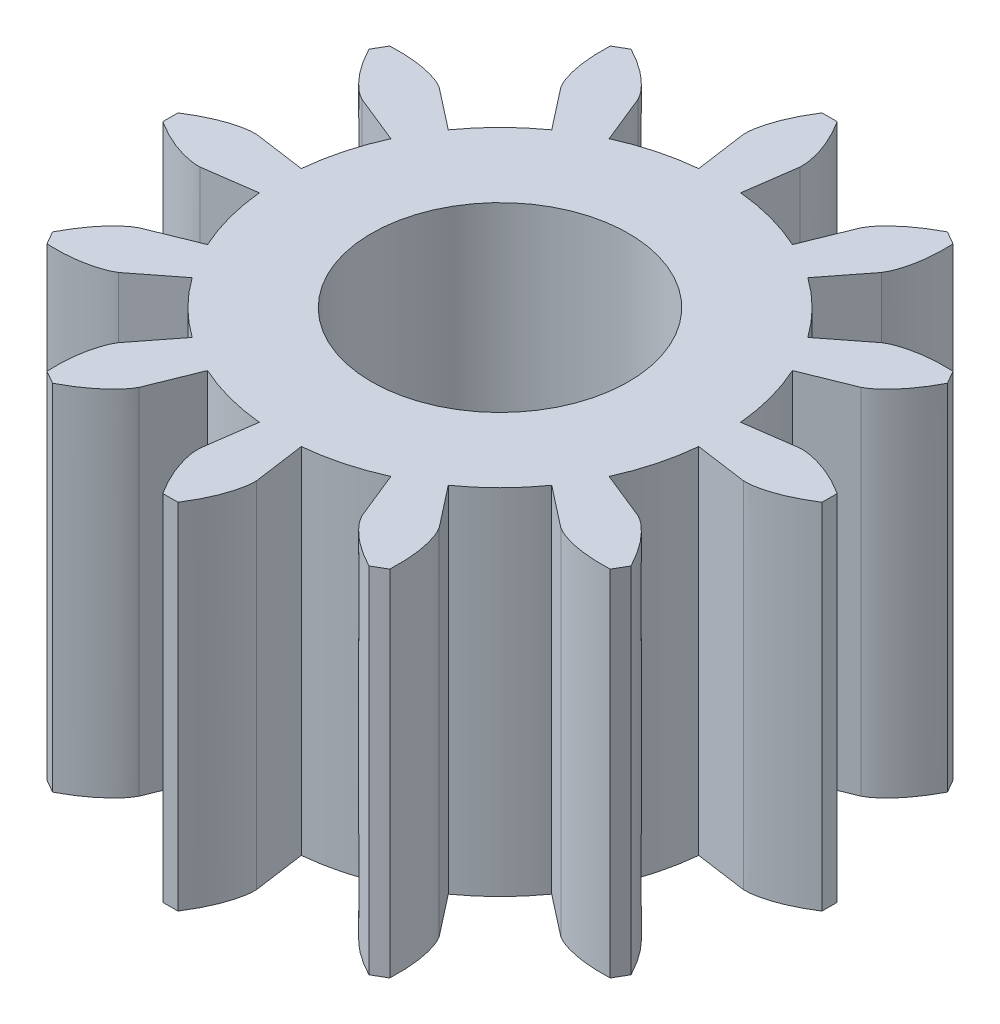
SolidWorks part; units mm, degrees
ref_plane "Front Plane" through (0, 0, 0) normal (0, 0, 1) x (1, 0, 0)
ref_plane "Top Plane" through (0, 0, 0) normal (0, 1, 0) x (1, 0, 0)
ref_plane "Right Plane" through (0, 0, 0) normal (1, 0, 0) x (0, 0, -1)
ref_plane "Plane1" through (0, -5, 0) normal (0, -1, 0) x (1, 0, 0)
sketch "Sketch1" plane through (0, -5, 0) normal (0, -1, 0) x (1, 0, 0)
  line L0 (3.7441, -2.923) -> (4.4442, -3.4696)
  line L1 (5.9256, -3.7266) -> (6.1901, -3.2684)
  line L2 (5.2268, -2.114) -> (4.4035, -1.781)
  line L3 (4.704, -0.6593) -> (5.5836, -0.7826)
  line L4 (6.995, -0.2646) -> (6.995, 0.2646)
  line L5 (5.5836, 0.7826) -> (4.704, 0.6593)
  line L6 (4.4035, 1.781) -> (5.2268, 2.114)
  line L7 (6.1901, 3.2684) -> (5.9256, 3.7266)
  line L8 (4.4442, 3.4696) -> (3.7441, 2.923)
  line L9 (2.923, 3.7441) -> (3.4696, 4.4442)
  line L10 (3.7266, 5.9256) -> (3.2684, 6.1901)
  line L11 (2.114, 5.2268) -> (1.781, 4.4035)
  line L12 (0.6593, 4.704) -> (0.7826, 5.5836)
  line L13 (0.2646, 6.995) -> (-0.2646, 6.995)
  line L14 (-0.7826, 5.5836) -> (-0.6593, 4.704)
  line L15 (-1.781, 4.4035) -> (-2.114, 5.2268)
  line L16 (-3.2684, 6.1901) -> (-3.7266, 5.9256)
  line L17 (-3.4696, 4.4442) -> (-2.923, 3.7441)
  line L18 (-3.7441, 2.923) -> (-4.4442, 3.4696)
  line L19 (-5.9256, 3.7266) -> (-6.1901, 3.2684)
  line L20 (-5.2268, 2.114) -> (-4.4035, 1.781)
  line L21 (-4.704, 0.6593) -> (-5.5836, 0.7826)
  line L22 (-6.995, 0.2646) -> (-6.995, -0.2646)
  line L23 (-5.5836, -0.7826) -> (-4.704, -0.6593)
  line L24 (-4.4035, -1.781) -> (-5.2268, -2.114)
  line L25 (-6.1901, -3.2684) -> (-5.9256, -3.7266)
  line L26 (-4.4442, -3.4696) -> (-3.7441, -2.923)
  line L27 (-2.923, -3.7441) -> (-3.4696, -4.4442)
  line L28 (-3.7266, -5.9256) -> (-3.2684, -6.1901)
  line L29 (-2.114, -5.2268) -> (-1.781, -4.4035)
  line L30 (-0.6593, -4.704) -> (-0.7826, -5.5836)
  line L31 (-0.2646, -6.995) -> (0.2646, -6.995)
  line L32 (0.7826, -5.5836) -> (0.6593, -4.704)
  line L33 (1.781, -4.4035) -> (2.114, -5.2268)
  line L34 (3.2684, -6.1901) -> (3.7266, -5.9256)
  line L35 (3.4696, -4.4442) -> (2.923, -3.7441)
  arc A0 (2.923, -3.7441) -> (3.7441, -2.923) centre (0, 0) ccw
  arc A1 (4.4035, -1.781) -> (4.704, -0.6593) centre (0, 0) ccw
  arc A2 (4.704, 0.6593) -> (4.4035, 1.781) centre (0, 0) ccw
  arc A3 (3.7441, 2.923) -> (2.923, 3.7441) centre (0, 0) ccw
  arc A4 (1.781, 4.4035) -> (0.6593, 4.704) centre (0, 0) ccw
  arc A5 (-0.6593, 4.704) -> (-1.781, 4.4035) centre (0, 0) ccw
  arc A6 (-2.923, 3.7441) -> (-3.7441, 2.923) centre (0, 0) ccw
  arc A7 (-4.4035, 1.781) -> (-4.704, 0.6593) centre (0, 0) ccw
  arc A8 (-4.704, -0.6593) -> (-4.4035, -1.781) centre (0, 0) ccw
  arc A9 (-3.7441, -2.923) -> (-2.923, -3.7441) centre (0, 0) ccw
  arc A10 (-1.781, -4.4035) -> (-0.6593, -4.704) centre (0, 0) ccw
  arc A11 (0.6593, -4.704) -> (1.781, -4.4035) centre (0, 0) ccw
  ellipse E0 centre (5.8654, -2.9875) end of major axis (7.546, -2.8631) minor radius 0.7415 (4.4442, -3.4696) -> (5.9256, -3.7266) ccw
  ellipse E1 centre (5.5279, -3.5513) end of major axis (6.2585, -5.0325) minor radius 0.7192 (6.1901, -3.2684) -> (5.2268, -2.114) ccw
  ellipse E2 centre (6.5733, 0.3454) end of major axis (7.9666, 1.2935) minor radius 0.7415 (5.5836, -0.7826) -> (6.995, -0.2646) ccw
  ellipse E3 centre (6.563, -0.3115) end of major axis (7.9362, -1.229) minor radius 0.7192 (6.995, 0.2646) -> (5.5836, 0.7826) ccw
  ellipse E4 centre (5.5199, 3.5858) end of major axis (4.7874, 2.068) minor radius 0.7415 (5.2268, 2.114) -> (6.1901, 3.2684) ccw
  ellipse E5 centre (5.8394, 3.0117) end of major axis (7.4875, 2.9038) minor radius 0.7192 (5.9256, 3.7266) -> (4.4442, 3.4696) ccw
  ellipse E6 centre (2.9875, 5.8654) end of major axis (3.112, 4.1847) minor radius 0.7415 (3.4696, 4.4442) -> (3.7266, 5.9256) ccw
  ellipse E7 centre (3.5513, 5.5279) end of major axis (5.0325, 6.2585) minor radius 0.7192 (3.2684, 6.1901) -> (2.114, 5.2268) ccw
  ellipse E8 centre (-0.3454, 6.5733) end of major axis (0.6027, 5.18) minor radius 0.7415 (0.7826, 5.5836) -> (0.2646, 6.995) ccw
  ellipse E9 centre (0.3115, 6.563) end of major axis (-0.606, 5.1897) minor radius 0.7192 (-0.2646, 6.995) -> (-0.7826, 5.5836) ccw
  ellipse E10 centre (-3.5858, 5.5199) end of major axis (-2.068, 4.7874) minor radius 0.7415 (-2.114, 5.2268) -> (-3.2684, 6.1901) ccw
  ellipse E11 centre (-3.0117, 5.8394) end of major axis (-3.1197, 4.1914) minor radius 0.7192 (-3.7266, 5.9256) -> (-3.4696, 4.4442) ccw
  ellipse E12 centre (-5.8654, 2.9875) end of major axis (-4.1847, 3.112) minor radius 0.7415 (-4.4442, 3.4696) -> (-5.9256, 3.7266) ccw
  ellipse E13 centre (-5.5279, 3.5513) end of major axis (-4.7974, 2.07) minor radius 0.7192 (-6.1901, 3.2684) -> (-5.2268, 2.114) ccw
  ellipse E14 centre (-6.5733, -0.3454) end of major axis (-5.18, 0.6027) minor radius 0.7415 (-5.5836, 0.7826) -> (-6.995, 0.2646) ccw
  ellipse E15 centre (-6.563, 0.3115) end of major axis (-5.1897, -0.606) minor radius 0.7192 (-6.995, -0.2646) -> (-5.5836, -0.7826) ccw
  ellipse E16 centre (-5.5199, -3.5858) end of major axis (-6.2525, -5.1035) minor radius 0.7415 (-5.2268, -2.114) -> (-6.1901, -3.2684) ccw
  ellipse E17 centre (-5.8394, -3.0117) end of major axis (-4.1914, -3.1197) minor radius 0.7192 (-5.9256, -3.7266) -> (-4.4442, -3.4696) ccw
  ellipse E18 centre (-2.9875, -5.8654) end of major axis (-2.8631, -7.546) minor radius 0.7415 (-3.4696, -4.4442) -> (-3.7266, -5.9256) ccw
  ellipse E19 centre (-3.5513, -5.5279) end of major axis (-5.0325, -6.2585) minor radius 0.7192 (-3.2684, -6.1901) -> (-2.114, -5.2268) ccw
  ellipse E20 centre (0.3454, -6.5733) end of major axis (1.2935, -7.9666) minor radius 0.7415 (-0.7826, -5.5836) -> (-0.2646, -6.995) ccw
  ellipse E21 centre (-0.3115, -6.563) end of major axis (-1.229, -7.9362) minor radius 0.7192 (0.2646, -6.995) -> (0.7826, -5.5836) ccw
  ellipse E22 centre (3.5858, -5.5199) end of major axis (5.1035, -6.2525) minor radius 0.7415 (2.114, -5.2268) -> (3.2684, -6.1901) ccw
  ellipse E23 centre (3.0117, -5.8394) end of major axis (2.9038, -7.4875) minor radius 0.7192 (3.7266, -5.9256) -> (3.4696, -4.4442) ccw
  point P4 (5.8654, -2.9875)
  point P5 (7.546, -2.8631)
  point P6 (5.9201, -3.727)
  point P7 (4.4442, -3.4696)
  point P8 (5.9256, -3.7266)
  point P9 (5.1439, -3.7018)
  point P10 (6.5868, -2.2732)
  point P18 (5.5279, -3.5513)
  point P19 (6.173, -3.2331)
  point P20 (6.2585, -5.0325)
  point P21 (6.1901, -3.2684)
  point P22 (5.2268, -2.114)
  point P23 (5.7778, -2.6038)
  point P24 (5.2781, -4.4987)
  point P34 (6.5733, 0.3454)
  point P35 (7.9666, 1.2935)
  point P36 (6.9905, -0.2677)
  point P37 (5.5836, -0.7826)
  point P38 (6.995, -0.2646)
  point P39 (6.3057, -0.6339)
  point P40 (6.8409, 1.3247)
  point P48 (6.563, -0.3115)
  point P49 (7.9362, -1.229)
  point P50 (6.1634, -0.9095)
  point P51 (6.995, 0.2646)
  point P52 (5.5836, 0.7826)
  point P53 (6.3057, 0.6339)
  point P54 (6.8203, -1.2569)
  point P64 (5.5199, 3.5858)
  point P65 (6.1878, 3.2634)
  point P66 (4.7874, 2.068)
  point P67 (5.2268, 2.114)
  point P68 (6.1901, 3.2684)
  point P69 (5.7778, 2.6038)
  point P70 (5.2621, 4.5677)
  point P78 (5.8394, 3.0117)
  point P79 (7.4875, 2.9038)
  point P80 (5.7924, 2.294)
  point P81 (5.9256, 3.7266)
  point P82 (4.4442, 3.4696)
  point P83 (5.1439, 3.7018)
  point P84 (6.535, 2.3216)
  point P94 (2.9875, 5.8654)
  point P95 (3.727, 5.9201)
  point P96 (3.112, 4.1847)
  point P97 (3.4696, 4.4442)
  point P98 (3.7266, 5.9256)
  point P99 (3.7018, 5.1439)
  point P100 (2.2732, 6.5868)
  point P108 (3.5513, 5.5279)
  point P109 (5.0325, 6.2585)
  point P110 (3.8694, 4.8829)
  point P111 (3.2684, 6.1901)
  point P112 (2.114, 5.2268)
  point P113 (2.6038, 5.7778)
  point P114 (4.4987, 5.2781)
  point P124 (-0.3454, 6.5733)
  point P125 (0.2677, 6.9905)
  point P126 (0.6027, 5.18)
  point P127 (0.7826, 5.5836)
  point P128 (0.2646, 6.995)
  point P129 (0.6339, 6.3057)
  point P130 (-1.3247, 6.8409)
  point P138 (0.3115, 6.563)
  point P139 (0.9095, 6.1634)
  point P140 (-0.606, 5.1897)
  point P141 (-0.2646, 6.995)
  point P142 (-0.7826, 5.5836)
  point P143 (-0.6339, 6.3057)
  point P144 (1.2569, 6.8203)
  point P154 (-3.5858, 5.5199)
  point P155 (-2.068, 4.7874)
  point P156 (-3.9081, 4.8521)
  point P157 (-2.114, 5.2268)
  point P158 (-3.2684, 6.1901)
  point P159 (-2.6038, 5.7778)
  point P160 (-4.5677, 5.2621)
  point P168 (-3.0117, 5.8394)
  point P169 (-2.294, 5.7924)
  point P170 (-3.1197, 4.1914)
  point P171 (-3.7266, 5.9256)
  point P172 (-3.4696, 4.4442)
  point P173 (-3.7018, 5.1439)
  point P174 (-2.3216, 6.535)
  point P184 (-5.8654, 2.9875)
  point P185 (-4.1847, 3.112)
  point P186 (-5.8106, 2.248)
  point P187 (-4.4442, 3.4696)
  point P188 (-5.9256, 3.7266)
  point P189 (-5.1439, 3.7018)
  point P190 (-6.5868, 2.2732)
  point P198 (-5.5279, 3.5513)
  point P199 (-4.8829, 3.8694)
  point P200 (-4.7974, 2.07)
  point P201 (-6.1901, 3.2684)
  point P202 (-5.2268, 2.114)
  point P203 (-5.7778, 2.6038)
  point P204 (-5.2781, 4.4987)
  point P214 (-6.5733, -0.3454)
  point P215 (-5.18, 0.6027)
  point P216 (-6.1561, -0.9585)
  point P217 (-5.5836, 0.7826)
  point P218 (-6.995, 0.2646)
  point P219 (-6.3057, 0.6339)
  point P220 (-6.8409, -1.3247)
  point P228 (-6.563, 0.3115)
  point P229 (-5.1897, -0.606)
  point P230 (-6.9625, -0.2865)
  point P231 (-6.995, -0.2646)
  point P232 (-5.5836, -0.7826)
  point P233 (-6.3057, -0.6339)
  point P234 (-6.8203, 1.2569)
  point P244 (-5.5199, -3.5858)
  point P245 (-4.8521, -3.9081)
  point P246 (-6.2525, -5.1035)
  point P247 (-5.2268, -2.114)
  point P248 (-6.1901, -3.2684)
  point P249 (-5.7778, -2.6038)
  point P250 (-5.2621, -4.5677)
  point P258 (-5.8394, -3.0117)
  point P259 (-4.1914, -3.1197)
  point P260 (-5.8865, -3.7294)
  point P261 (-5.9256, -3.7266)
  point P262 (-4.4442, -3.4696)
  point P263 (-5.1439, -3.7018)
  point P264 (-6.535, -2.3216)
  point P274 (-2.9875, -5.8654)
  point P275 (-2.248, -5.8106)
  point P276 (-2.8631, -7.546)
  point P277 (-3.4696, -4.4442)
  point P278 (-3.7266, -5.9256)
  point P279 (-3.7018, -5.1439)
  point P280 (-2.2732, -6.5868)
  point P288 (-3.5513, -5.5279)
  point P289 (-2.07, -4.7974)
  point P290 (-3.2331, -6.173)
  point P291 (-3.2684, -6.1901)
  point P292 (-2.114, -5.2268)
  point P293 (-2.6038, -5.7778)
  point P294 (-4.4987, -5.2781)
  point P304 (0.3454, -6.5733)
  point P305 (0.9585, -6.1561)
  point P306 (1.2935, -7.9666)
  point P307 (-0.7826, -5.5836)
  point P308 (-0.2646, -6.995)
  point P309 (-0.6339, -6.3057)
  point P310 (1.3247, -6.8409)
  point P318 (-0.3115, -6.563)
  point P319 (0.2865, -6.9625)
  point P320 (-1.229, -7.9362)
  point P321 (0.2646, -6.995)
  point P322 (0.7826, -5.5836)
  point P323 (0.6339, -6.3057)
  point P324 (-1.2569, -6.8203)
  point P334 (3.5858, -5.5199)
  point P335 (5.1035, -6.2525)
  point P336 (3.2634, -6.1878)
  point P337 (2.114, -5.2268)
  point P338 (3.2684, -6.1901)
  point P339 (2.6038, -5.7778)
  point P340 (4.5677, -5.2621)
  point P348 (3.0117, -5.8394)
  point P349 (3.7294, -5.8865)
  point P350 (2.9038, -7.4875)
  point P351 (3.7266, -5.9256)
  point P352 (3.4696, -4.4442)
  point P353 (3.7018, -5.1439)
  point P354 (2.3216, -6.535)
extrude "Boss-Extrude1" add sketch "Sketch1" against normal blind 5
sketch "Sketch3" plane through (0, 0, 0) normal (0, 1, 0) x (1, 0, 0)
  line L36 (2.923, 3.7441) -> (3.4696, 4.4442)
  line L37 (3.7266, 5.9256) -> (3.2684, 6.1901)
  line L38 (2.114, 5.2268) -> (1.781, 4.4035)
  line L39 (0.6593, 4.704) -> (0.7826, 5.5836)
  line L40 (0.2646, 6.995) -> (-0.2646, 6.995)
  line L41 (-0.7826, 5.5836) -> (-0.6593, 4.704)
  line L42 (-1.781, 4.4035) -> (-2.114, 5.2268)
  line L43 (-3.2684, 6.1901) -> (-3.7266, 5.9256)
  line L44 (-3.4696, 4.4442) -> (-2.923, 3.7441)
  line L45 (-3.7441, 2.923) -> (-4.4442, 3.4696)
  line L46 (-5.9256, 3.7266) -> (-6.1901, 3.2684)
  line L47 (-5.2268, 2.114) -> (-4.4035, 1.781)
  line L48 (-4.704, 0.6593) -> (-5.5836, 0.7826)
  line L49 (-6.995, 0.2646) -> (-6.995, -0.2646)
  line L50 (-5.5836, -0.7826) -> (-4.704, -0.6593)
  line L51 (-4.4035, -1.781) -> (-5.2268, -2.114)
  line L52 (-6.1901, -3.2684) -> (-5.9256, -3.7266)
  line L53 (-4.4442, -3.4696) -> (-3.7441, -2.923)
  line L54 (-2.923, -3.7441) -> (-3.4696, -4.4442)
  line L55 (-3.7266, -5.9256) -> (-3.2684, -6.1901)
  line L56 (-2.114, -5.2268) -> (-1.781, -4.4035)
  line L57 (-0.6593, -4.704) -> (-0.7826, -5.5836)
  line L58 (-0.2646, -6.995) -> (0.2646, -6.995)
  line L59 (0.7826, -5.5836) -> (0.6593, -4.704)
  line L60 (1.781, -4.4035) -> (2.114, -5.2268)
  line L61 (3.2684, -6.1901) -> (3.7266, -5.9256)
  line L62 (3.4696, -4.4442) -> (2.923, -3.7441)
  line L63 (3.7441, -2.923) -> (4.4442, -3.4696)
  line L64 (5.9256, -3.7266) -> (6.1901, -3.2684)
  line L65 (5.2268, -2.114) -> (4.4035, -1.781)
  line L66 (4.704, -0.6593) -> (5.5836, -0.7826)
  line L67 (6.995, -0.2646) -> (6.995, 0.2646)
  line L68 (5.5836, 0.7826) -> (4.704, 0.6593)
  line L69 (4.4035, 1.781) -> (5.2268, 2.114)
  line L70 (6.1901, 3.2684) -> (5.9256, 3.7266)
  line L71 (4.4442, 3.4696) -> (3.7441, 2.923)
  line L72 (2.923, 3.7441) -> (3.4696, 4.4442)
  line L73 (3.7266, 5.9256) -> (3.2684, 6.1901)
  line L74 (2.114, 5.2268) -> (1.781, 4.4035)
  line L75 (0.6593, 4.704) -> (0.7826, 5.5836)
  line L76 (0.2646, 6.995) -> (-0.2646, 6.995)
  line L77 (-0.7826, 5.5836) -> (-0.6593, 4.704)
  line L78 (-1.781, 4.4035) -> (-2.114, 5.2268)
  line L79 (-3.2684, 6.1901) -> (-3.7266, 5.9256)
  line L80 (-3.4696, 4.4442) -> (-2.923, 3.7441)
  line L81 (-3.7441, 2.923) -> (-4.4442, 3.4696)
  line L82 (-5.9256, 3.7266) -> (-6.1901, 3.2684)
  line L83 (-5.2268, 2.114) -> (-4.4035, 1.781)
  line L84 (-4.704, 0.6593) -> (-5.5836, 0.7826)
  line L85 (-6.995, 0.2646) -> (-6.995, -0.2646)
  line L86 (-5.5836, -0.7826) -> (-4.704, -0.6593)
  line L87 (-4.4035, -1.781) -> (-5.2268, -2.114)
  line L88 (-6.1901, -3.2684) -> (-5.9256, -3.7266)
  line L89 (-4.4442, -3.4696) -> (-3.7441, -2.923)
  line L90 (-2.923, -3.7441) -> (-3.4696, -4.4442)
  line L91 (-3.7266, -5.9256) -> (-3.2684, -6.1901)
  line L92 (-2.114, -5.2268) -> (-1.781, -4.4035)
  line L93 (-0.6593, -4.704) -> (-0.7826, -5.5836)
  line L94 (-0.2646, -6.995) -> (0.2646, -6.995)
  line L95 (0.7826, -5.5836) -> (0.6593, -4.704)
  line L96 (1.781, -4.4035) -> (2.114, -5.2268)
  line L97 (3.2684, -6.1901) -> (3.7266, -5.9256)
  line L98 (3.4696, -4.4442) -> (2.923, -3.7441)
  line L99 (3.7441, -2.923) -> (4.4442, -3.4696)
  line L100 (5.9256, -3.7266) -> (6.1901, -3.2684)
  line L101 (5.2268, -2.114) -> (4.4035, -1.781)
  line L102 (4.704, -0.6593) -> (5.5836, -0.7826)
  line L103 (6.995, -0.2646) -> (6.995, 0.2646)
  line L104 (5.5836, 0.7826) -> (4.704, 0.6593)
  line L105 (4.4035, 1.781) -> (5.2268, 2.114)
  line L106 (6.1901, 3.2684) -> (5.9256, 3.7266)
  line L107 (4.4442, 3.4696) -> (3.7441, 2.923)
  arc A12 (3.7441, 2.923) -> (2.923, 3.7441) centre (0, 0) ccw
  arc A13 (1.781, 4.4035) -> (0.6593, 4.704) centre (0, 0) ccw
  arc A14 (-0.6593, 4.704) -> (-1.781, 4.4035) centre (0, 0) ccw
  arc A15 (-2.923, 3.7441) -> (-3.7441, 2.923) centre (0, 0) ccw
  arc A16 (-4.4035, 1.781) -> (-4.704, 0.6593) centre (0, 0) ccw
  arc A17 (-4.704, -0.6593) -> (-4.4035, -1.781) centre (0, 0) ccw
  arc A18 (-3.7441, -2.923) -> (-2.923, -3.7441) centre (0, 0) ccw
  arc A19 (-1.781, -4.4035) -> (-0.6593, -4.704) centre (0, 0) ccw
  arc A20 (0.6593, -4.704) -> (1.781, -4.4035) centre (0, 0) ccw
  arc A21 (2.923, -3.7441) -> (3.7441, -2.923) centre (0, 0) ccw
  arc A22 (4.4035, -1.781) -> (4.704, -0.6593) centre (0, 0) ccw
  arc A23 (4.704, 0.6593) -> (4.4035, 1.781) centre (0, 0) ccw
  arc A24 (3.7441, 2.923) -> (2.923, 3.7441) centre (0, 0) ccw
  arc A25 (1.781, 4.4035) -> (0.6593, 4.704) centre (0, 0) ccw
  arc A26 (-0.6593, 4.704) -> (-1.781, 4.4035) centre (0, 0) ccw
  arc A27 (-2.923, 3.7441) -> (-3.7441, 2.923) centre (0, 0) ccw
  arc A28 (-4.4035, 1.781) -> (-4.704, 0.6593) centre (0, 0) ccw
  arc A29 (-4.704, -0.6593) -> (-4.4035, -1.781) centre (0, 0) ccw
  arc A30 (-3.7441, -2.923) -> (-2.923, -3.7441) centre (0, 0) ccw
  arc A31 (-1.781, -4.4035) -> (-0.6593, -4.704) centre (0, 0) ccw
  arc A32 (0.6593, -4.704) -> (1.781, -4.4035) centre (0, 0) ccw
  arc A33 (2.923, -3.7441) -> (3.7441, -2.923) centre (0, 0) ccw
  arc A34 (4.4035, -1.781) -> (4.704, -0.6593) centre (0, 0) ccw
  arc A35 (4.704, 0.6593) -> (4.4035, 1.781) centre (0, 0) ccw
  ellipse E24 centre (3.0117, 5.8394) end of major axis (2.9038, 7.4875) minor radius 0.7192 (3.4696, 4.4442) -> (3.7266, 5.9256) ccw
  ellipse E25 centre (3.5858, 5.5199) end of major axis (2.068, 4.7874) minor radius 0.7415 (3.2684, 6.1901) -> (2.114, 5.2268) ccw
  ellipse E26 centre (-0.3115, 6.563) end of major axis (-1.229, 7.9362) minor radius 0.7192 (0.7826, 5.5836) -> (0.2646, 6.995) ccw
  ellipse E27 centre (0.3454, 6.5733) end of major axis (1.2935, 7.9666) minor radius 0.7415 (-0.2646, 6.995) -> (-0.7826, 5.5836) ccw
  ellipse E28 centre (-3.5513, 5.5279) end of major axis (-2.07, 4.7974) minor radius 0.7192 (-2.114, 5.2268) -> (-3.2684, 6.1901) ccw
  ellipse E29 centre (-2.9875, 5.8654) end of major axis (-2.8631, 7.546) minor radius 0.7415 (-3.7266, 5.9256) -> (-3.4696, 4.4442) ccw
  ellipse E30 centre (-5.8394, 3.0117) end of major axis (-4.1914, 3.1197) minor radius 0.7192 (-4.4442, 3.4696) -> (-5.9256, 3.7266) ccw
  ellipse E31 centre (-5.5199, 3.5858) end of major axis (-6.2525, 5.1035) minor radius 0.7415 (-6.1901, 3.2684) -> (-5.2268, 2.114) ccw
  ellipse E32 centre (-6.563, -0.3115) end of major axis (-5.1897, 0.606) minor radius 0.7192 (-5.5836, 0.7826) -> (-6.995, 0.2646) ccw
  ellipse E33 centre (-6.5733, 0.3454) end of major axis (-7.9666, 1.2935) minor radius 0.7415 (-6.995, -0.2646) -> (-5.5836, -0.7826) ccw
  ellipse E34 centre (-5.5279, -3.5513) end of major axis (-6.2585, -5.0325) minor radius 0.7192 (-5.2268, -2.114) -> (-6.1901, -3.2684) ccw
  ellipse E35 centre (-5.8654, -2.9875) end of major axis (-4.1847, -3.112) minor radius 0.7415 (-5.9256, -3.7266) -> (-4.4442, -3.4696) ccw
  ellipse E36 centre (-3.0117, -5.8394) end of major axis (-3.1197, -4.1914) minor radius 0.7192 (-3.4696, -4.4442) -> (-3.7266, -5.9256) ccw
  ellipse E37 centre (-3.5858, -5.5199) end of major axis (-5.1035, -6.2525) minor radius 0.7415 (-3.2684, -6.1901) -> (-2.114, -5.2268) ccw
  ellipse E38 centre (0.3115, -6.563) end of major axis (-0.606, -5.1897) minor radius 0.7192 (-0.7826, -5.5836) -> (-0.2646, -6.995) ccw
  ellipse E39 centre (-0.3454, -6.5733) end of major axis (0.6027, -5.18) minor radius 0.7415 (0.2646, -6.995) -> (0.7826, -5.5836) ccw
  ellipse E40 centre (3.5513, -5.5279) end of major axis (5.0325, -6.2585) minor radius 0.7192 (2.114, -5.2268) -> (3.2684, -6.1901) ccw
  ellipse E41 centre (2.9875, -5.8654) end of major axis (3.112, -4.1847) minor radius 0.7415 (3.7266, -5.9256) -> (3.4696, -4.4442) ccw
  ellipse E42 centre (5.8394, -3.0117) end of major axis (7.4875, -2.9038) minor radius 0.7192 (4.4442, -3.4696) -> (5.9256, -3.7266) ccw
  ellipse E43 centre (5.5199, -3.5858) end of major axis (4.7874, -2.068) minor radius 0.7415 (6.1901, -3.2684) -> (5.2268, -2.114) ccw
  ellipse E44 centre (6.563, 0.3115) end of major axis (7.9362, 1.229) minor radius 0.7192 (5.5836, -0.7826) -> (6.995, -0.2646) ccw
  ellipse E45 centre (6.5733, -0.3454) end of major axis (7.9666, -1.2935) minor radius 0.7415 (6.995, 0.2646) -> (5.5836, 0.7826) ccw
  ellipse E46 centre (5.5279, 3.5513) end of major axis (6.2585, 5.0325) minor radius 0.7192 (5.2268, 2.114) -> (6.1901, 3.2684) ccw
  ellipse E47 centre (5.8654, 2.9875) end of major axis (7.546, 2.8631) minor radius 0.7415 (5.9256, 3.7266) -> (4.4442, 3.4696) ccw
  ellipse E48 centre (3.0117, 5.8394) end of major axis (2.9038, 7.4875) minor radius 0.7192 (3.4696, 4.4442) -> (3.7266, 5.9256) ccw
  ellipse E49 centre (3.5858, 5.5199) end of major axis (5.1035, 6.2525) minor radius 0.7415 (3.2684, 6.1901) -> (2.114, 5.2268) ccw
  ellipse E50 centre (-0.3115, 6.563) end of major axis (-1.229, 7.9362) minor radius 0.7192 (0.7826, 5.5836) -> (0.2646, 6.995) ccw
  ellipse E51 centre (0.3454, 6.5733) end of major axis (1.2935, 7.9666) minor radius 0.7415 (-0.2646, 6.995) -> (-0.7826, 5.5836) ccw
  ellipse E52 centre (-3.5513, 5.5279) end of major axis (-2.07, 4.7974) minor radius 0.7192 (-2.114, 5.2268) -> (-3.2684, 6.1901) ccw
  ellipse E53 centre (-2.9875, 5.8654) end of major axis (-2.8631, 7.546) minor radius 0.7415 (-3.7266, 5.9256) -> (-3.4696, 4.4442) ccw
  ellipse E54 centre (-5.8394, 3.0117) end of major axis (-4.1914, 3.1197) minor radius 0.7192 (-4.4442, 3.4696) -> (-5.9256, 3.7266) ccw
  ellipse E55 centre (-5.5199, 3.5858) end of major axis (-6.2525, 5.1035) minor radius 0.7415 (-6.1901, 3.2684) -> (-5.2268, 2.114) ccw
  ellipse E56 centre (-6.563, -0.3115) end of major axis (-5.1897, 0.606) minor radius 0.7192 (-5.5836, 0.7826) -> (-6.995, 0.2646) ccw
  ellipse E57 centre (-6.5733, 0.3454) end of major axis (-7.9666, 1.2935) minor radius 0.7415 (-6.995, -0.2646) -> (-5.5836, -0.7826) ccw
  ellipse E58 centre (-5.5279, -3.5513) end of major axis (-6.2585, -5.0325) minor radius 0.7192 (-5.2268, -2.114) -> (-6.1901, -3.2684) ccw
  ellipse E59 centre (-5.8654, -2.9875) end of major axis (-4.1847, -3.112) minor radius 0.7415 (-5.9256, -3.7266) -> (-4.4442, -3.4696) ccw
  ellipse E60 centre (-3.0117, -5.8394) end of major axis (-3.1197, -4.1914) minor radius 0.7192 (-3.4696, -4.4442) -> (-3.7266, -5.9256) ccw
  ellipse E61 centre (-3.5858, -5.5199) end of major axis (-5.1035, -6.2525) minor radius 0.7415 (-3.2684, -6.1901) -> (-2.114, -5.2268) ccw
  ellipse E62 centre (0.3115, -6.563) end of major axis (-0.606, -5.1897) minor radius 0.7192 (-0.7826, -5.5836) -> (-0.2646, -6.995) ccw
  ellipse E63 centre (-0.3454, -6.5733) end of major axis (0.6027, -5.18) minor radius 0.7415 (0.2646, -6.995) -> (0.7826, -5.5836) ccw
  ellipse E64 centre (3.5513, -5.5279) end of major axis (5.0325, -6.2585) minor radius 0.7192 (2.114, -5.2268) -> (3.2684, -6.1901) ccw
  ellipse E65 centre (2.9875, -5.8654) end of major axis (3.112, -4.1847) minor radius 0.7415 (3.7266, -5.9256) -> (3.4696, -4.4442) ccw
  ellipse E66 centre (5.8394, -3.0117) end of major axis (7.4875, -2.9038) minor radius 0.7192 (4.4442, -3.4696) -> (5.9256, -3.7266) ccw
  ellipse E67 centre (5.5199, -3.5858) end of major axis (4.7874, -2.068) minor radius 0.7415 (6.1901, -3.2684) -> (5.2268, -2.114) ccw
  ellipse E68 centre (6.563, 0.3115) end of major axis (7.9362, 1.229) minor radius 0.7192 (5.5836, -0.7826) -> (6.995, -0.2646) ccw
  ellipse E69 centre (6.5733, -0.3454) end of major axis (7.9666, -1.2935) minor radius 0.7415 (6.995, 0.2646) -> (5.5836, 0.7826) ccw
  ellipse E70 centre (5.5279, 3.5513) end of major axis (6.2585, 5.0325) minor radius 0.7192 (5.2268, 2.114) -> (6.1901, 3.2684) ccw
  ellipse E71 centre (5.8654, 2.9875) end of major axis (7.546, 2.8631) minor radius 0.7415 (5.9256, 3.7266) -> (4.4442, 3.4696) ccw
  dimension "D1" = 0
extrude "Boss-Extrude2" add sketch "Sketch3" along normal blind 2.3
sketch "Sketch2" plane through (0, -5, 0) normal (0, 1, 0) x (1, 0, 0)
  line L0 (0.4329, 4.5294) -> (0.5832, 5.6016)
  line L1 (0.1571, 6.795) -> (-0.1571, 6.795)
  line L2 (-0.5832, 5.6015) -> (-0.4329, 4.5294)
  line L3 (-1.8898, 4.139) -> (-2.2957, 5.1427)
  line L4 (-3.2614, 5.9632) -> (-3.5336, 5.8061)
  line L5 (-3.3058, 4.5594) -> (-2.6396, 3.7061)
  line L6 (-3.7061, 2.6396) -> (-4.5595, 3.3059)
  line L7 (-5.8061, 3.5336) -> (-5.9632, 3.2614)
  line L8 (-5.1426, 2.2957) -> (-4.139, 1.8898)
  line L9 (-4.5294, 0.4329) -> (-5.6016, 0.5832)
  line L10 (-6.795, 0.1571) -> (-6.795, -0.1571)
  line L11 (-5.6015, -0.5832) -> (-4.5294, -0.4329)
  line L12 (-4.139, -1.8898) -> (-5.1427, -2.2957)
  line L13 (-5.9632, -3.2614) -> (-5.8061, -3.5336)
  line L14 (-4.5594, -3.3058) -> (-3.7061, -2.6396)
  line L15 (-2.6396, -3.7061) -> (-3.3059, -4.5595)
  line L16 (-3.5336, -5.8061) -> (-3.2614, -5.9632)
  line L17 (-2.2957, -5.1426) -> (-1.8898, -4.139)
  line L18 (-0.4329, -4.5294) -> (-0.5832, -5.6016)
  line L19 (-0.1571, -6.795) -> (0.1571, -6.795)
  line L20 (0.5832, -5.6015) -> (0.4329, -4.5294)
  line L21 (1.8898, -4.139) -> (2.2957, -5.1427)
  line L22 (3.2614, -5.9632) -> (3.5336, -5.8061)
  line L23 (3.3058, -4.5594) -> (2.6396, -3.7061)
  line L24 (3.7061, -2.6396) -> (4.5595, -3.3059)
  line L25 (5.8061, -3.5336) -> (5.9632, -3.2614)
  line L26 (5.1426, -2.2957) -> (4.139, -1.8898)
  line L27 (4.5294, -0.4329) -> (5.6016, -0.5832)
  line L28 (6.795, -0.1571) -> (6.795, 0.1571)
  line L29 (5.6015, 0.5832) -> (4.5294, 0.4329)
  line L30 (4.139, 1.8898) -> (5.1427, 2.2957)
  line L31 (5.9632, 3.2614) -> (5.8061, 3.5336)
  line L32 (4.5594, 3.3058) -> (3.7061, 2.6396)
  line L33 (2.6396, 3.7061) -> (3.3059, 4.5595)
  line L34 (3.5336, 5.8061) -> (3.2614, 5.9632)
  line L35 (2.2957, 5.1426) -> (1.8898, 4.139)
  line L36 (2.923, 3.7441) -> (3.4696, 4.4442)
  line L37 (3.7266, 5.9256) -> (3.2684, 6.1901)
  line L38 (2.114, 5.2268) -> (1.781, 4.4035)
  line L39 (0.6593, 4.704) -> (0.7826, 5.5836)
  line L40 (0.2646, 6.995) -> (-0.2646, 6.995)
  line L41 (-0.7826, 5.5836) -> (-0.6593, 4.704)
  line L42 (-1.781, 4.4035) -> (-2.114, 5.2268)
  line L43 (-3.2684, 6.1901) -> (-3.7266, 5.9256)
  line L44 (-3.4696, 4.4442) -> (-2.923, 3.7441)
  line L45 (-3.7441, 2.923) -> (-4.4442, 3.4696)
  line L46 (-5.9256, 3.7266) -> (-6.1901, 3.2684)
  line L47 (-5.2268, 2.114) -> (-4.4035, 1.781)
  line L48 (-4.704, 0.6593) -> (-5.5836, 0.7826)
  line L49 (-6.995, 0.2646) -> (-6.995, -0.2646)
  line L50 (-5.5836, -0.7826) -> (-4.704, -0.6593)
  line L51 (-4.4035, -1.781) -> (-5.2268, -2.114)
  line L52 (-6.1901, -3.2684) -> (-5.9256, -3.7266)
  line L53 (-4.4442, -3.4696) -> (-3.7441, -2.923)
  line L54 (-2.923, -3.7441) -> (-3.4696, -4.4442)
  line L55 (-3.7266, -5.9256) -> (-3.2684, -6.1901)
  line L56 (-2.114, -5.2268) -> (-1.781, -4.4035)
  line L57 (-0.6593, -4.704) -> (-0.7826, -5.5836)
  line L58 (-0.2646, -6.995) -> (0.2646, -6.995)
  line L59 (0.7826, -5.5836) -> (0.6593, -4.704)
  line L60 (1.781, -4.4035) -> (2.114, -5.2268)
  line L61 (3.2684, -6.1901) -> (3.7266, -5.9256)
  line L62 (3.4696, -4.4442) -> (2.923, -3.7441)
  line L63 (3.7441, -2.923) -> (4.4442, -3.4696)
  line L64 (5.9256, -3.7266) -> (6.1901, -3.2684)
  line L65 (5.2268, -2.114) -> (4.4035, -1.781)
  line L66 (4.704, -0.6593) -> (5.5836, -0.7826)
  line L67 (6.995, -0.2646) -> (6.995, 0.2646)
  line L68 (5.5836, 0.7826) -> (4.704, 0.6593)
  line L69 (4.4035, 1.781) -> (5.2268, 2.114)
  line L70 (6.1901, 3.2684) -> (5.9256, 3.7266)
  line L71 (4.4442, 3.4696) -> (3.7441, 2.923)
  line L72 (2.923, 3.7441) -> (3.4696, 4.4442)
  line L73 (3.7266, 5.9256) -> (3.2684, 6.1901)
  line L74 (2.114, 5.2268) -> (1.781, 4.4035)
  line L75 (0.6593, 4.704) -> (0.7826, 5.5836)
  line L76 (0.2646, 6.995) -> (-0.2646, 6.995)
  line L77 (-0.7826, 5.5836) -> (-0.6593, 4.704)
  line L78 (-1.781, 4.4035) -> (-2.114, 5.2268)
  line L79 (-3.2684, 6.1901) -> (-3.7266, 5.9256)
  line L80 (-3.4696, 4.4442) -> (-2.923, 3.7441)
  line L81 (-3.7441, 2.923) -> (-4.4442, 3.4696)
  line L82 (-5.9256, 3.7266) -> (-6.1901, 3.2684)
  line L83 (-5.2268, 2.114) -> (-4.4035, 1.781)
  line L84 (-4.704, 0.6593) -> (-5.5836, 0.7826)
  line L85 (-6.995, 0.2646) -> (-6.995, -0.2646)
  line L86 (-5.5836, -0.7826) -> (-4.704, -0.6593)
  line L87 (-4.4035, -1.781) -> (-5.2268, -2.114)
  line L88 (-6.1901, -3.2684) -> (-5.9256, -3.7266)
  line L89 (-4.4442, -3.4696) -> (-3.7441, -2.923)
  line L90 (-2.923, -3.7441) -> (-3.4696, -4.4442)
  line L91 (-3.7266, -5.9256) -> (-3.2684, -6.1901)
  line L92 (-2.114, -5.2268) -> (-1.781, -4.4035)
  line L93 (-0.6593, -4.704) -> (-0.7826, -5.5836)
  line L94 (-0.2646, -6.995) -> (0.2646, -6.995)
  line L95 (0.7826, -5.5836) -> (0.6593, -4.704)
  line L96 (1.781, -4.4035) -> (2.114, -5.2268)
  line L97 (3.2684, -6.1901) -> (3.7266, -5.9256)
  line L98 (3.4696, -4.4442) -> (2.923, -3.7441)
  line L99 (3.7441, -2.923) -> (4.4442, -3.4696)
  line L100 (5.9256, -3.7266) -> (6.1901, -3.2684)
  line L101 (5.2268, -2.114) -> (4.4035, -1.781)
  line L102 (4.704, -0.6593) -> (5.5836, -0.7826)
  line L103 (6.995, -0.2646) -> (6.995, 0.2646)
  line L104 (5.5836, 0.7826) -> (4.704, 0.6593)
  line L105 (4.4035, 1.781) -> (5.2268, 2.114)
  line L106 (6.1901, 3.2684) -> (5.9256, 3.7266)
  line L107 (4.4442, 3.4696) -> (3.7441, 2.923)
  circle A0 centre (0, 0) radius 2.65
  arc A1 (1.8898, 4.139) -> (0.4329, 4.5294) centre (0, 0) ccw
  arc A2 (-0.4329, 4.5294) -> (-1.8898, 4.139) centre (0, 0) ccw
  arc A3 (-2.6396, 3.7061) -> (-3.7061, 2.6396) centre (0, 0) ccw
  arc A4 (-4.139, 1.8898) -> (-4.5294, 0.4329) centre (0, 0) ccw
  arc A5 (-4.5294, -0.4329) -> (-4.139, -1.8898) centre (0, 0) ccw
  arc A6 (-3.7061, -2.6396) -> (-2.6396, -3.7061) centre (0, 0) ccw
  arc A7 (-1.8898, -4.139) -> (-0.4329, -4.5294) centre (0, 0) ccw
  arc A8 (0.4329, -4.5294) -> (1.8898, -4.139) centre (0, 0) ccw
  arc A9 (2.6396, -3.7061) -> (3.7061, -2.6396) centre (0, 0) ccw
  arc A10 (4.139, -1.8898) -> (4.5294, -0.4329) centre (0, 0) ccw
  arc A11 (4.5294, 0.4329) -> (4.139, 1.8898) centre (0, 0) ccw
  arc A12 (3.7061, 2.6396) -> (2.6396, 3.7061) centre (0, 0) ccw
  arc A13 (3.7441, 2.923) -> (2.923, 3.7441) centre (0, 0) ccw
  arc A14 (1.781, 4.4035) -> (0.6593, 4.704) centre (0, 0) ccw
  arc A15 (-0.6593, 4.704) -> (-1.781, 4.4035) centre (0, 0) ccw
  arc A16 (-2.923, 3.7441) -> (-3.7441, 2.923) centre (0, 0) ccw
  arc A17 (-4.4035, 1.781) -> (-4.704, 0.6593) centre (0, 0) ccw
  arc A18 (-4.704, -0.6593) -> (-4.4035, -1.781) centre (0, 0) ccw
  arc A19 (-3.7441, -2.923) -> (-2.923, -3.7441) centre (0, 0) ccw
  arc A20 (-1.781, -4.4035) -> (-0.6593, -4.704) centre (0, 0) ccw
  arc A21 (0.6593, -4.704) -> (1.781, -4.4035) centre (0, 0) ccw
  arc A22 (2.923, -3.7441) -> (3.7441, -2.923) centre (0, 0) ccw
  arc A23 (4.4035, -1.781) -> (4.704, -0.6593) centre (0, 0) ccw
  arc A24 (4.704, 0.6593) -> (4.4035, 1.781) centre (0, 0) ccw
  arc A25 (3.7441, 2.923) -> (2.923, 3.7441) centre (0, 0) ccw
  arc A26 (1.781, 4.4035) -> (0.6593, 4.704) centre (0, 0) ccw
  arc A27 (-0.6593, 4.704) -> (-1.781, 4.4035) centre (0, 0) ccw
  arc A28 (-2.923, 3.7441) -> (-3.7441, 2.923) centre (0, 0) ccw
  arc A29 (-4.4035, 1.781) -> (-4.704, 0.6593) centre (0, 0) ccw
  arc A30 (-4.704, -0.6593) -> (-4.4035, -1.781) centre (0, 0) ccw
  arc A31 (-3.7441, -2.923) -> (-2.923, -3.7441) centre (0, 0) ccw
  arc A32 (-1.781, -4.4035) -> (-0.6593, -4.704) centre (0, 0) ccw
  arc A33 (0.6593, -4.704) -> (1.781, -4.4035) centre (0, 0) ccw
  arc A34 (2.923, -3.7441) -> (3.7441, -2.923) centre (0, 0) ccw
  arc A35 (4.4035, -1.781) -> (4.704, -0.6593) centre (0, 0) ccw
  arc A36 (4.704, 0.6593) -> (4.4035, 1.781) centre (0, 0) ccw
  arc A37 (1.8898, 4.139) -> (0.4329, 4.5294) centre (0, 0) ccw construction
  ellipse E24 centre (3.0117, 5.8394) end of major axis (2.9038, 7.4875) minor radius 0.7192 (3.4696, 4.4442) -> (3.7266, 5.9256) ccw
  ellipse E25 centre (3.5858, 5.5199) end of major axis (2.068, 4.7874) minor radius 0.7415 (3.2684, 6.1901) -> (2.114, 5.2268) ccw
  ellipse E26 centre (-0.3115, 6.563) end of major axis (-1.229, 7.9362) minor radius 0.7192 (0.7826, 5.5836) -> (0.2646, 6.995) ccw
  ellipse E27 centre (0.3454, 6.5733) end of major axis (1.2935, 7.9666) minor radius 0.7415 (-0.2646, 6.995) -> (-0.7826, 5.5836) ccw
  ellipse E28 centre (-3.5513, 5.5279) end of major axis (-2.07, 4.7974) minor radius 0.7192 (-2.114, 5.2268) -> (-3.2684, 6.1901) ccw
  ellipse E29 centre (-2.9875, 5.8654) end of major axis (-2.8631, 7.546) minor radius 0.7415 (-3.7266, 5.9256) -> (-3.4696, 4.4442) ccw
  ellipse E30 centre (-5.8394, 3.0117) end of major axis (-4.1914, 3.1197) minor radius 0.7192 (-4.4442, 3.4696) -> (-5.9256, 3.7266) ccw
  ellipse E31 centre (-5.5199, 3.5858) end of major axis (-6.2525, 5.1035) minor radius 0.7415 (-6.1901, 3.2684) -> (-5.2268, 2.114) ccw
  ellipse E32 centre (-6.563, -0.3115) end of major axis (-5.1897, 0.606) minor radius 0.7192 (-5.5836, 0.7826) -> (-6.995, 0.2646) ccw
  ellipse E33 centre (-6.5733, 0.3454) end of major axis (-7.9666, 1.2935) minor radius 0.7415 (-6.995, -0.2646) -> (-5.5836, -0.7826) ccw
  ellipse E34 centre (-5.5279, -3.5513) end of major axis (-6.2585, -5.0325) minor radius 0.7192 (-5.2268, -2.114) -> (-6.1901, -3.2684) ccw
  ellipse E35 centre (-5.8654, -2.9875) end of major axis (-4.1847, -3.112) minor radius 0.7415 (-5.9256, -3.7266) -> (-4.4442, -3.4696) ccw
  ellipse E36 centre (-3.0117, -5.8394) end of major axis (-3.1197, -4.1914) minor radius 0.7192 (-3.4696, -4.4442) -> (-3.7266, -5.9256) ccw
  ellipse E37 centre (-3.5858, -5.5199) end of major axis (-2.068, -4.7874) minor radius 0.7415 (-3.2684, -6.1901) -> (-2.114, -5.2268) ccw
  ellipse E38 centre (0.3115, -6.563) end of major axis (-0.606, -5.1897) minor radius 0.7192 (-0.7826, -5.5836) -> (-0.2646, -6.995) ccw
  ellipse E39 centre (-0.3454, -6.5733) end of major axis (0.6027, -5.18) minor radius 0.7415 (0.2646, -6.995) -> (0.7826, -5.5836) ccw
  ellipse E40 centre (3.5513, -5.5279) end of major axis (5.0325, -6.2585) minor radius 0.7192 (2.114, -5.2268) -> (3.2684, -6.1901) ccw
  ellipse E41 centre (2.9875, -5.8654) end of major axis (3.112, -4.1847) minor radius 0.7415 (3.7266, -5.9256) -> (3.4696, -4.4442) ccw
  ellipse E42 centre (5.8394, -3.0117) end of major axis (7.4875, -2.9038) minor radius 0.7192 (4.4442, -3.4696) -> (5.9256, -3.7266) ccw
  ellipse E43 centre (5.5199, -3.5858) end of major axis (4.7874, -2.068) minor radius 0.7415 (6.1901, -3.2684) -> (5.2268, -2.114) ccw
  ellipse E44 centre (6.563, 0.3115) end of major axis (7.9362, 1.229) minor radius 0.7192 (5.5836, -0.7826) -> (6.995, -0.2646) ccw
  ellipse E45 centre (6.5733, -0.3454) end of major axis (7.9666, -1.2935) minor radius 0.7415 (6.995, 0.2646) -> (5.5836, 0.7826) ccw
  ellipse E46 centre (5.5279, 3.5513) end of major axis (6.2585, 5.0325) minor radius 0.7192 (5.2268, 2.114) -> (6.1901, 3.2684) ccw
  ellipse E47 centre (5.8654, 2.9875) end of major axis (7.546, 2.8631) minor radius 0.7415 (5.9256, 3.7266) -> (4.4442, 3.4696) ccw
  ellipse E48 centre (3.0117, 5.8394) end of major axis (2.9038, 7.4875) minor radius 0.7192 (3.4696, 4.4442) -> (3.7266, 5.9256) ccw
  ellipse E49 centre (3.5858, 5.5199) end of major axis (5.1035, 6.2525) minor radius 0.7415 (3.2684, 6.1901) -> (2.114, 5.2268) ccw
  ellipse E50 centre (-0.3115, 6.563) end of major axis (-1.229, 7.9362) minor radius 0.7192 (0.7826, 5.5836) -> (0.2646, 6.995) ccw
  ellipse E51 centre (0.3454, 6.5733) end of major axis (1.2935, 7.9666) minor radius 0.7415 (-0.2646, 6.995) -> (-0.7826, 5.5836) ccw
  ellipse E52 centre (-3.5513, 5.5279) end of major axis (-2.07, 4.7974) minor radius 0.7192 (-2.114, 5.2268) -> (-3.2684, 6.1901) ccw
  ellipse E53 centre (-2.9875, 5.8654) end of major axis (-2.8631, 7.546) minor radius 0.7415 (-3.7266, 5.9256) -> (-3.4696, 4.4442) ccw
  ellipse E54 centre (-5.8394, 3.0117) end of major axis (-4.1914, 3.1197) minor radius 0.7192 (-4.4442, 3.4696) -> (-5.9256, 3.7266) ccw
  ellipse E55 centre (-5.5199, 3.5858) end of major axis (-6.2525, 5.1035) minor radius 0.7415 (-6.1901, 3.2684) -> (-5.2268, 2.114) ccw
  ellipse E56 centre (-6.563, -0.3115) end of major axis (-5.1897, 0.606) minor radius 0.7192 (-5.5836, 0.7826) -> (-6.995, 0.2646) ccw
  ellipse E57 centre (-6.5733, 0.3454) end of major axis (-7.9666, 1.2935) minor radius 0.7415 (-6.995, -0.2646) -> (-5.5836, -0.7826) ccw
  ellipse E58 centre (-5.5279, -3.5513) end of major axis (-6.2585, -5.0325) minor radius 0.7192 (-5.2268, -2.114) -> (-6.1901, -3.2684) ccw
  ellipse E59 centre (-5.8654, -2.9875) end of major axis (-4.1847, -3.112) minor radius 0.7415 (-5.9256, -3.7266) -> (-4.4442, -3.4696) ccw
  ellipse E60 centre (-3.0117, -5.8394) end of major axis (-3.1197, -4.1914) minor radius 0.7192 (-3.4696, -4.4442) -> (-3.7266, -5.9256) ccw
  ellipse E61 centre (-3.5858, -5.5199) end of major axis (-2.068, -4.7874) minor radius 0.7415 (-3.2684, -6.1901) -> (-2.114, -5.2268) ccw
  ellipse E62 centre (0.3115, -6.563) end of major axis (-0.606, -5.1897) minor radius 0.7192 (-0.7826, -5.5836) -> (-0.2646, -6.995) ccw
  ellipse E63 centre (-0.3454, -6.5733) end of major axis (0.6027, -5.18) minor radius 0.7415 (0.2646, -6.995) -> (0.7826, -5.5836) ccw
  ellipse E64 centre (3.5513, -5.5279) end of major axis (5.0325, -6.2585) minor radius 0.7192 (2.114, -5.2268) -> (3.2684, -6.1901) ccw
  ellipse E65 centre (2.9875, -5.8654) end of major axis (3.112, -4.1847) minor radius 0.7415 (3.7266, -5.9256) -> (3.4696, -4.4442) ccw
  ellipse E66 centre (5.8394, -3.0117) end of major axis (7.4875, -2.9038) minor radius 0.7192 (4.4442, -3.4696) -> (5.9256, -3.7266) ccw
  ellipse E67 centre (5.5199, -3.5858) end of major axis (4.7874, -2.068) minor radius 0.7415 (6.1901, -3.2684) -> (5.2268, -2.114) ccw
  ellipse E68 centre (6.563, 0.3115) end of major axis (7.9362, 1.229) minor radius 0.7192 (5.5836, -0.7826) -> (6.995, -0.2646) ccw
  ellipse E69 centre (6.5733, -0.3454) end of major axis (7.9666, -1.2935) minor radius 0.7415 (6.995, 0.2646) -> (5.5836, 0.7826) ccw
  ellipse E70 centre (5.5279, 3.5513) end of major axis (6.2585, 5.0325) minor radius 0.7192 (5.2268, 2.114) -> (6.1901, 3.2684) ccw
  ellipse E71 centre (5.8654, 2.9875) end of major axis (7.546, 2.8631) minor radius 0.7415 (5.9256, 3.7266) -> (4.4442, 3.4696) ccw
  spline S0 degree 1 poles (0.5832, 5.6016) (0.1571, 6.795) knots 0 0 1 1 construction
  spline S1 degree 1 poles (-0.1571, 6.795) (-0.5832, 5.6015) knots 0 0 1 1 construction
  spline S2 degree 1 poles (-2.2957, 5.1427) (-3.2614, 5.9632) knots 0 0 1 1 construction
  spline S3 degree 1 poles (-3.5336, 5.8061) (-3.3058, 4.5594) knots 0 0 1 1 construction
  spline S4 degree 1 poles (-4.5595, 3.3059) (-5.8061, 3.5336) knots 0 0 1 1 construction
  spline S5 degree 1 poles (-5.9632, 3.2614) (-5.1426, 2.2957) knots 0 0 1 1 construction
  spline S6 degree 1 poles (-5.6016, 0.5832) (-6.795, 0.1571) knots 0 0 1 1 construction
  spline S7 degree 1 poles (-6.795, -0.1571) (-5.6015, -0.5832) knots 0 0 1 1 construction
  spline S8 degree 1 poles (-5.1427, -2.2957) (-5.9632, -3.2614) knots 0 0 1 1 construction
  spline S9 degree 1 poles (-5.8061, -3.5336) (-4.5594, -3.3058) knots 0 0 1 1 construction
  spline S10 degree 1 poles (-3.3059, -4.5595) (-3.5336, -5.8061) knots 0 0 1 1 construction
  spline S11 degree 1 poles (-3.2614, -5.9632) (-2.2957, -5.1426) knots 0 0 1 1 construction
  spline S12 degree 1 poles (-0.5832, -5.6016) (-0.1571, -6.795) knots 0 0 1 1 construction
  spline S13 degree 1 poles (0.1571, -6.795) (0.5832, -5.6015) knots 0 0 1 1 construction
  spline S14 degree 1 poles (2.2957, -5.1427) (3.2614, -5.9632) knots 0 0 1 1 construction
  spline S15 degree 1 poles (3.5336, -5.8061) (3.3058, -4.5594) knots 0 0 1 1 construction
  spline S16 degree 1 poles (4.5595, -3.3059) (5.8061, -3.5336) knots 0 0 1 1 construction
  spline S17 degree 1 poles (5.9632, -3.2614) (5.1426, -2.2957) knots 0 0 1 1 construction
  spline S18 degree 1 poles (5.6016, -0.5832) (6.795, -0.1571) knots 0 0 1 1 construction
  spline S19 degree 1 poles (6.795, 0.1571) (5.6015, 0.5832) knots 0 0 1 1 construction
  spline S20 degree 1 poles (5.1427, 2.2957) (5.9632, 3.2614) knots 0 0 1 1 construction
  spline S21 degree 1 poles (5.8061, 3.5336) (4.5594, 3.3058) knots 0 0 1 1 construction
  spline S22 degree 1 poles (3.3059, 4.5595) (3.5336, 5.8061) knots 0 0 1 1 construction
  spline S23 degree 1 poles (3.2614, 5.9632) (2.2957, 5.1426) knots 0 0 1 1 construction
  spline S24 degree 3 poles (0.5832, 5.6016) (0.586, 5.6826) (0.5725, 5.8291) (0.4916, 6.1375) (0.3528, 6.4638) (0.2253, 6.6887) (0.1571, 6.795) knots -2.597712 -2.597712 -2.597712 -2.597712 -2.351759 -2.105807 -1.859855 -1.613903 -1.613903 -1.613903 -1.613903
  spline S25 degree 3 poles (-0.1571, 6.795) (-0.2253, 6.6887) (-0.353, 6.4635) (-0.4915, 6.1378) (-0.5723, 5.8301) (-0.5859, 5.6827) (-0.5832, 5.6015) knots 1.633086 1.633086 1.633086 1.633086 1.874753 2.116419 2.358085 2.599751 2.599751 2.599751 2.599751
  spline S26 degree 3 poles (-2.2957, 5.1427) (-2.3338, 5.2143) (-2.4187, 5.3344) (-2.643, 5.561) (-2.9264, 5.7742) (-3.1493, 5.9053) (-3.2614, 5.9632) knots 0.543881 0.543881 0.543881 0.543881 0.789833 1.035785 1.281738 1.52769 1.52769 1.52769 1.52769
  spline S27 degree 3 poles (-3.5336, 5.8061) (-3.5394, 5.6799) (-3.5374, 5.421) (-3.4946, 5.0698) (-3.4107, 4.7628) (-3.3488, 4.6284) (-3.3058, 4.5594) knots 1.633086 1.633086 1.633086 1.633086 1.874753 2.116419 2.358085 2.599751 2.599751 2.599751 2.599751
  spline S28 degree 3 poles (-4.5595, 3.3059) (-4.6283, 3.3488) (-4.7619, 3.4104) (-5.0694, 3.4945) (-5.4214, 3.5374) (-5.68, 3.5395) (-5.8061, 3.5336) knots 0.543881 0.543881 0.543881 0.543881 0.789833 1.035785 1.281738 1.52769 1.52769 1.52769 1.52769
  spline S29 degree 3 poles (-5.9632, 3.2614) (-5.9052, 3.1492) (-5.774, 2.926) (-5.5613, 2.6433) (-5.3352, 2.4194) (-5.2144, 2.3339) (-5.1426, 2.2957) knots 1.633086 1.633086 1.633086 1.633086 1.874753 2.116419 2.358085 2.599751 2.599751 2.599751 2.599751
  spline S30 degree 3 poles (-5.6016, 0.5832) (-5.6826, 0.586) (-5.8291, 0.5725) (-6.1375, 0.4916) (-6.4638, 0.3528) (-6.6887, 0.2253) (-6.795, 0.1571) knots 0.543881 0.543881 0.543881 0.543881 0.789833 1.035785 1.281738 1.52769 1.52769 1.52769 1.52769
  spline S31 degree 3 poles (-6.795, -0.1571) (-6.6887, -0.2253) (-6.4635, -0.353) (-6.1378, -0.4915) (-5.8301, -0.5723) (-5.6827, -0.5859) (-5.6015, -0.5832) knots -1.508506 -1.508506 -1.508506 -1.508506 -1.26684 -1.025174 -0.783508 -0.541842 -0.541842 -0.541842 -0.541842
  spline S32 degree 3 poles (-5.1427, -2.2957) (-5.2143, -2.3338) (-5.3344, -2.4187) (-5.561, -2.643) (-5.7742, -2.9264) (-5.9053, -3.1493) (-5.9632, -3.2614) knots 0.543881 0.543881 0.543881 0.543881 0.789833 1.035785 1.281738 1.52769 1.52769 1.52769 1.52769
  spline S33 degree 3 poles (-5.8061, -3.5336) (-5.6799, -3.5394) (-5.421, -3.5374) (-5.0698, -3.4946) (-4.7628, -3.4107) (-4.6284, -3.3488) (-4.5594, -3.3058) knots -1.508506 -1.508506 -1.508506 -1.508506 -1.26684 -1.025174 -0.783508 -0.541842 -0.541842 -0.541842 -0.541842
  spline S34 degree 3 poles (-3.3059, -4.5595) (-3.3488, -4.6283) (-3.4104, -4.7619) (-3.4945, -5.0694) (-3.5374, -5.4214) (-3.5395, -5.68) (-3.5336, -5.8061) knots 0.543881 0.543881 0.543881 0.543881 0.789833 1.035785 1.281738 1.52769 1.52769 1.52769 1.52769
  spline S35 degree 3 poles (-3.2614, -5.9632) (-3.1492, -5.9052) (-2.926, -5.774) (-2.6433, -5.5613) (-2.4194, -5.3352) (-2.3339, -5.2144) (-2.2957, -5.1426) knots -1.508506 -1.508506 -1.508506 -1.508506 -1.26684 -1.025174 -0.783508 -0.541842 -0.541842 -0.541842 -0.541842
  spline S36 degree 3 poles (-0.5832, -5.6016) (-0.586, -5.6826) (-0.5725, -5.8291) (-0.4916, -6.1375) (-0.3528, -6.4638) (-0.2253, -6.6887) (-0.1571, -6.795) knots 0.543881 0.543881 0.543881 0.543881 0.789833 1.035785 1.281738 1.52769 1.52769 1.52769 1.52769
  spline S37 degree 3 poles (0.1571, -6.795) (0.2253, -6.6887) (0.353, -6.4635) (0.4915, -6.1378) (0.5723, -5.8301) (0.5859, -5.6827) (0.5832, -5.6015) knots -1.508506 -1.508506 -1.508506 -1.508506 -1.26684 -1.025174 -0.783508 -0.541842 -0.541842 -0.541842 -0.541842
  spline S38 degree 3 poles (2.2957, -5.1427) (2.3338, -5.2143) (2.4187, -5.3344) (2.643, -5.561) (2.9264, -5.7742) (3.1493, -5.9053) (3.2614, -5.9632) knots -2.597712 -2.597712 -2.597712 -2.597712 -2.351759 -2.105807 -1.859855 -1.613903 -1.613903 -1.613903 -1.613903
  spline S39 degree 3 poles (3.5336, -5.8061) (3.5394, -5.6799) (3.5374, -5.421) (3.4946, -5.0698) (3.4107, -4.7628) (3.3488, -4.6284) (3.3058, -4.5594) knots -1.508506 -1.508506 -1.508506 -1.508506 -1.26684 -1.025174 -0.783508 -0.541842 -0.541842 -0.541842 -0.541842
  spline S40 degree 3 poles (4.5595, -3.3059) (4.6283, -3.3488) (4.7619, -3.4104) (5.0694, -3.4945) (5.4214, -3.5374) (5.68, -3.5395) (5.8061, -3.5336) knots -2.597712 -2.597712 -2.597712 -2.597712 -2.351759 -2.105807 -1.859855 -1.613903 -1.613903 -1.613903 -1.613903
  spline S41 degree 3 poles (5.9632, -3.2614) (5.9052, -3.1492) (5.774, -2.926) (5.5613, -2.6433) (5.3352, -2.4194) (5.2144, -2.3339) (5.1426, -2.2957) knots -1.508506 -1.508506 -1.508506 -1.508506 -1.26684 -1.025174 -0.783508 -0.541842 -0.541842 -0.541842 -0.541842
  spline S42 degree 3 poles (5.6016, -0.5832) (5.6826, -0.586) (5.8291, -0.5725) (6.1375, -0.4916) (6.4638, -0.3528) (6.6887, -0.2253) (6.795, -0.1571) knots -2.597712 -2.597712 -2.597712 -2.597712 -2.351759 -2.105807 -1.859855 -1.613903 -1.613903 -1.613903 -1.613903
  spline S43 degree 3 poles (6.795, 0.1571) (6.6887, 0.2253) (6.4635, 0.353) (6.1378, 0.4915) (5.8301, 0.5723) (5.6827, 0.5859) (5.6015, 0.5832) knots 1.633086 1.633086 1.633086 1.633086 1.874753 2.116419 2.358085 2.599751 2.599751 2.599751 2.599751
  spline S44 degree 3 poles (5.1427, 2.2957) (5.2143, 2.3338) (5.3344, 2.4187) (5.561, 2.643) (5.7742, 2.9264) (5.9053, 3.1493) (5.9632, 3.2614) knots -2.597712 -2.597712 -2.597712 -2.597712 -2.351759 -2.105807 -1.859855 -1.613903 -1.613903 -1.613903 -1.613903
  spline S45 degree 3 poles (5.8061, 3.5336) (5.6799, 3.5394) (5.421, 3.5374) (5.0698, 3.4946) (4.7628, 3.4107) (4.6284, 3.3488) (4.5594, 3.3058) knots 1.633086 1.633086 1.633086 1.633086 1.874753 2.116419 2.358085 2.599751 2.599751 2.599751 2.599751
  spline S46 degree 3 poles (3.3059, 4.5595) (3.3488, 4.6283) (3.4104, 4.7619) (3.4945, 5.0694) (3.5374, 5.4214) (3.5395, 5.68) (3.5336, 5.8061) knots -2.597712 -2.597712 -2.597712 -2.597712 -2.351759 -2.105807 -1.859855 -1.613903 -1.613903 -1.613903 -1.613903
  spline S47 degree 3 poles (3.2614, 5.9632) (3.1492, 5.9052) (2.926, 5.774) (2.6433, 5.5613) (2.4194, 5.3352) (2.3339, 5.2144) (2.2957, 5.1426) knots 1.633086 1.633086 1.633086 1.633086 1.874753 2.116419 2.358085 2.599751 2.599751 2.599751 2.599751
  point P0 (3.7266, -5.9256)
  dimension "D1" = 5.3
  dimension "D2" = 0
  dimension "D3" = 0.2
extrude "Cut-Extrude1" cut sketch "Sketch2" against normal through all both and the other way through all contours A0 | E71 L106 E70 L105 A36 L104 E69 L103 E68 L102 A35 L101 E67 L100 E66 L99 A34 L98 E65 L97 E64 L96 A33 L95 E63 L94 E62 L93 A32 L92 E61 L91 E60 L90 A31 L89 E59 L88 E58 L87 A30 L86 E57 L85 E56 L84 A29 L83 E55 L82 E54 region at (3.2189, -5, -3.2189) region at (0, -5, 0)
